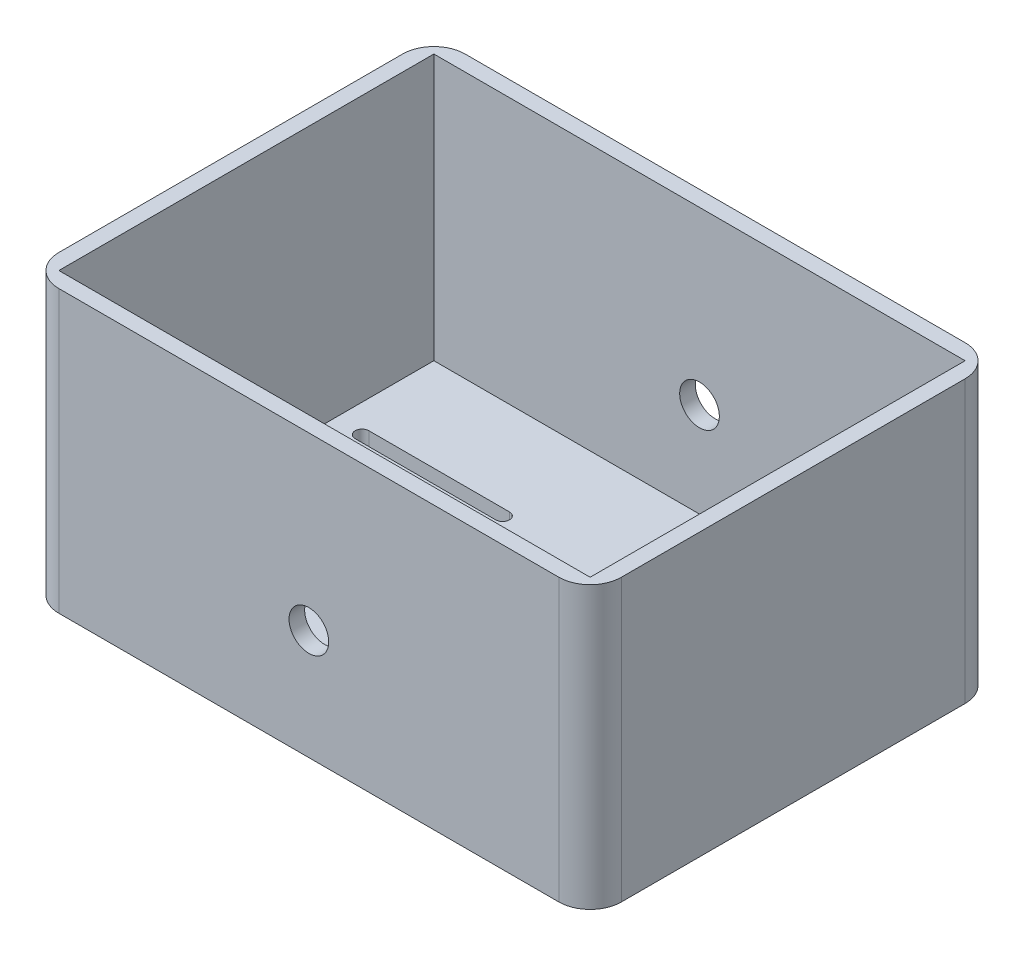
SolidWorks part; units mm, degrees
ref_plane "Plan de face" through (0, 0, 0) normal (0, 0, 1) x (1, 0, 0)
ref_plane "Plan de dessus" through (0, 0, 0) normal (0, 1, 0) x (1, 0, 0)
ref_plane "Plan de droite" through (0, 0, 0) normal (1, 0, 0) x (0, 0, -1)
sketch "Esquisse1" plane through (0, 0, 0) normal (0, 1, 0) x (1, 0, 0)
  line L1 (85, -60) -> (-85, -60)
  line L2 (85, -60) -> (85, 60)
  line L3 (85, 60) -> (-85, 60)
  line L4 (-85, -60) -> (-85, 60)
  line L5 (85, -60) -> (-85, 60) construction
  line L6 (85, 60) -> (-85, -60) construction
  line L7 (-90, -65) -> (90, -65)
  line L8 (-90, -65) -> (-90, 65)
  line L9 (-90, 65) -> (90, 65)
  line L10 (90, -65) -> (90, 65)
  line L11 (-90, -65) -> (90, 65) construction
  line L12 (-90, 65) -> (90, -65) construction
  point P0 (0, 0)
  point P5 (0, 0)
  dimension "D1" = 120
  dimension "D2" = 170
  dimension "D3" = 5
  dimension "D4" = 5
extrude "Boss.-Extru.2" add sketch "Esquisse1" along normal blind 90
sketch "Esquisse2" plane through (0, 0, 0) normal (0, 1, 0) x (1, 0, 0)
  line L1 (-85, 60) -> (85, 60)
  line L2 (-85, 60) -> (-85, -60)
  line L3 (-85, -60) -> (85, -60)
  line L4 (85, 60) -> (85, -60)
extrude "Boss.-Extru.3" add sketch "Esquisse2" along normal blind 5
sketch "Esquisse3" plane through (0, 5, 0) normal (0, 1, 0) x (1, 0, 0)
  circle A0 centre (0, 0) radius 20
  dimension "D1" = 40
extrude "Enlèv. mat.-Extru.1" cut sketch "Esquisse3" against normal through all
sketch "Esquisse4" plane through (0, 5, 0) normal (0, 1, 0) x (1, 0, 0)
  line L1 (85, 60) -> (-85, 60) construction
  line L2 (0, 60) -> (0, -60) construction
  line L3 (-85, -60) -> (85, -60) construction
  line L5 (-76, 28) -> (-31, 28) construction
  line L6 (-76, 30.2) -> (-31, 30.2)
  line L7 (-76, 25.8) -> (-31, 25.8)
  line L8 (-76, 16) -> (-31, 16) construction
  line L9 (-76, 18.2) -> (-31, 18.2)
  line L10 (-76, 13.8) -> (-31, 13.8)
  line L11 (-85, 60) -> (-85, -60) construction
  arc A0 (-76, 30.2) -> (-76, 25.8) centre (-76, 28) ccw
  arc A1 (-31, 25.8) -> (-31, 30.2) centre (-31, 28) ccw
  arc A2 (-76, 18.2) -> (-76, 13.8) centre (-76, 16) ccw
  arc A3 (-31, 13.8) -> (-31, 18.2) centre (-31, 16) ccw
  point P5 (0, 0)
  point P14 (-53.5, 28)
  point P21 (-53.5, 16)
  dimension "D1" = 2.2
  dimension "D2" = 45
  dimension "D3" = 12
  dimension "D4" = 9
  dimension "D5" = 32
extrude "Enlèv. mat.-Extru.2" cut sketch "Esquisse4" against normal through all
sketch "Esquisse5" plane through (0, 0, -65) normal (0, 0, -1) x (-1, 0, 0)
  line L3 (0, 90) -> (0, 0) construction
  line L4 (-90, 90) -> (90, 90) construction
  line L5 (-90, 0) -> (90, 0) construction
  circle A0 centre (0, 35.25) radius 6.35
  dimension "D1" = 12.7
  dimension "D2" = 35.25
extrude "Enlèv. mat.-Extru.3" cut sketch "Esquisse5" against normal up to surface (130 mm away) up to face at (0, 45, 65)
sketch "Esquisse6" plane through (0, 5, 0) normal (0, 1, 0) x (1, 0, 0)
  line L1 (26.12, 41.6) -> (29.12, 41.6)
  line L2 (26.12, 41.6) -> (26.12, -60)
  line L3 (26.12, -60) -> (29.12, -60)
  line L4 (29.12, 41.6) -> (29.12, -60)
  line L10 (85, -60) -> (85, 60) construction
  line L11 (85, -60) -> (-85, -60) construction
  dimension "D1" = 3
  dimension "D2" = 101.6
  dimension "D3" = 55.88
extrude "Boss.-Extru.4" add sketch "Esquisse6" along normal blind 20
fillet "Congé1" radius 10 4 edges at (90, 45, 65) (90, 45, -65) (-90, 45, -65) (-90, 45, 65)
